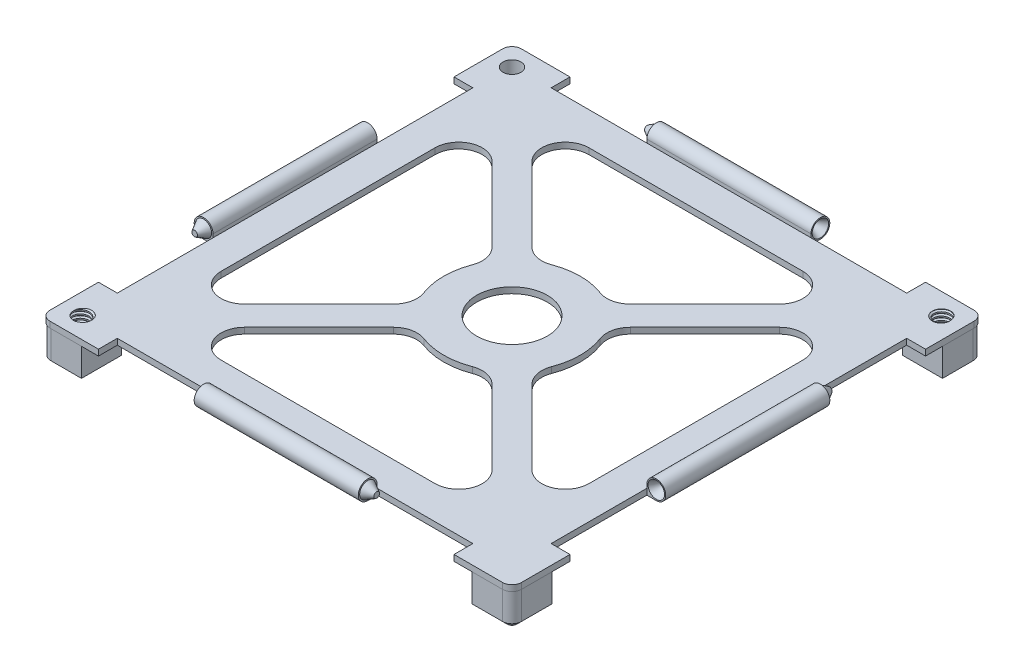
SolidWorks part; units mm, degrees
material "6061 Alloy"
ref_plane "Front Plane" through (0, 0, 0) normal (0, 0, 1) x (1, 0, 0)
ref_plane "Top Plane" through (0, 0, 0) normal (0, 1, 0) x (1, 0, 0)
ref_plane "Right Plane" through (0, 0, 0) normal (1, 0, 0) x (0, 0, -1)
sketch "X-Axis" plane through (0, 0, 0) normal (0, 1, 0) x (1, 0, 0)
  line L2 (-10, 0) -> (10, 0)
  point P3 (0, 0)
  dimension "D1" = 20
sketch "Y-Axis" plane through (0, 0, 0) normal (0, 1, 0) x (1, 0, 0)
  line L0 (0, -10) -> (0, 10)
  dimension "D1" = 20
sketch "Z-Axis" plane through (0, 0, 0) normal (1, 0, 0) x (0, 0, -1)
  line L0 (0, 10) -> (0, -10)
  line L1 (0, 55) -> (0, -55) construction
  point P5 (0, 0)
  dimension "D1" = 20
ref_axis "Axis1" through (0, 0, 0) along (0, 1, 0)
sketch "Sketch1" plane through (0, 0, 0) normal (0, 1, 0) x (1, 0, 0)
  line L0 (-10.4535, 14.6961) -> (-26.2218, 30.4645)
  line L1 (-46, -46) -> (46, -46)
  line L2 (-46, -46) -> (-46, 46)
  line L3 (-46, 46) -> (46, 46)
  line L4 (46, -46) -> (46, 46)
  line L5 (-46, -46) -> (46, 46) construction
  line L6 (-46, 46) -> (46, -46) construction
  line L7 (-22.6863, 39) -> (22.6863, 39)
  line L8 (26.2218, 30.4645) -> (10.4535, 14.6961)
  line L9 (30.4645, -26.2218) -> (14.6961, -10.4535)
  line L10 (14.6961, 10.4535) -> (30.4645, 26.2218)
  line L11 (39, 22.6863) -> (39, -22.6863)
  line L12 (-26.2218, -30.4645) -> (-10.4535, -14.6961)
  line L13 (10.4535, -14.6961) -> (26.2218, -30.4645)
  line L14 (22.6863, -39) -> (-22.6863, -39)
  line L15 (-30.4645, 26.2218) -> (-14.6961, 10.4535)
  line L16 (-14.6961, -10.4535) -> (-30.4645, -26.2218)
  line L17 (-39, -22.6863) -> (-39, 22.6863)
  circle A0 centre (0, 0) radius 7.5
  arc A1 (-5.1441, 13.5569) -> (5.1441, 13.5569) centre (0, 0) cw
  arc A2 (-5.1441, 13.5569) -> (-10.4535, 14.6961) centre (-6.9179, 18.2316) cw
  arc A3 (5.1441, 13.5569) -> (10.4535, 14.6961) centre (6.9179, 18.2316) ccw
  arc A4 (22.6863, 39) -> (26.2218, 30.4645) centre (22.6863, 34) cw
  arc A5 (-26.2218, 30.4645) -> (-22.6863, 39) centre (-22.6863, 34) cw
  arc A6 (13.5569, -5.1441) -> (14.6961, -10.4535) centre (18.2316, -6.9179) ccw
  arc A7 (13.5569, 5.1441) -> (13.5569, -5.1441) centre (0, 0) cw
  arc A8 (13.5569, 5.1441) -> (14.6961, 10.4535) centre (18.2316, 6.9179) cw
  arc A9 (30.4645, 26.2218) -> (39, 22.6863) centre (34, 22.6863) cw
  arc A10 (39, -22.6863) -> (30.4645, -26.2218) centre (34, -22.6863) cw
  arc A11 (-5.1441, -13.5569) -> (-10.4535, -14.6961) centre (-6.9179, -18.2316) ccw
  arc A12 (5.1441, -13.5569) -> (-5.1441, -13.5569) centre (0, 0) cw
  arc A13 (5.1441, -13.5569) -> (10.4535, -14.6961) centre (6.9179, -18.2316) cw
  arc A14 (26.2218, -30.4645) -> (22.6863, -39) centre (22.6863, -34) cw
  arc A15 (-22.6863, -39) -> (-26.2218, -30.4645) centre (-22.6863, -34) cw
  arc A16 (-13.5569, 5.1441) -> (-14.6961, 10.4535) centre (-18.2316, 6.9179) ccw
  arc A17 (-13.5569, -5.1441) -> (-13.5569, 5.1441) centre (0, 0) cw
  arc A18 (-13.5569, -5.1441) -> (-14.6961, -10.4535) centre (-18.2316, -6.9179) cw
  arc A19 (-30.4645, -26.2218) -> (-39, -22.6863) centre (-34, -22.6863) cw
  arc A20 (-39, 22.6863) -> (-30.4645, 26.2218) centre (-34, 22.6863) cw
  point P0 (0, 0)
  point P59 (0, 0)
  dimension "D3" = 15
  dimension "D6" = 7
  dimension "D8" = 5
  dimension "D1" = 92
  dimension "D2" = 92
  dimension "D4" = 6
  dimension "D5" = 6
  dimension "D7" = 7
  dimension "D9" = 4
extrude "Boss-Extrude1" add sketch "Sketch1" along normal blind 1.27
sketch "Sketch6" plane through (0, 0, 0) normal (0, 0, 1) x (1, 0, 0)
  line L0 (46, 2) -> (46, 0)
  line L1 (46, 0) -> (48, 0)
  line L2 (0, 0) -> (0, 69.0457) construction
  arc A0 (46, 2) -> (48, 0) centre (48, 2) cw
  dimension "D1" = 50
extrude "Boss-Extrude3" add sketch "Sketch6" along normal mid plane 34.8
sketch "Sketch7" plane through (0, 0, 17.4) normal (0, 0, 1) x (1, 0, 0)
  circle A0 centre (48, 2) radius 1.75
  dimension "D1" = 3.5
extrude "Cut-Extrude2" cut sketch "Sketch7" against normal blind 2 draft 30
sketch "Sketch8" plane through (0, 0, -17.4) normal (0, 0, -1) x (-1, 0, 0)
  circle A0 centre (-48, 2) radius 1.7
  dimension "D1" = 3.4
extrude "Boss-Extrude4" add sketch "Sketch8" along normal blind 1.9 draft 30
pattern_circular "CirPattern1" count 4 over 360 about axis through (0, 0, 0) along (0, 1, 0) of "Boss-Extrude3", "Cut-Extrude2", "Boss-Extrude4"
sketch "Sketch16" plane through (0, 0, 0) normal (0, -1, 0) x (1, 0, 0)
  line L1 (-50, 50) -> (-37.7, 50)
  line L2 (-50, 50) -> (-50, 37.7)
  line L3 (-50, 37.7) -> (-37.7, 37.7)
  line L4 (-37.7, 50) -> (-37.7, 37.7)
  dimension "D1" = 50
  dimension "D2" = 50
  dimension "D3" = 37.7
extrude "Boss-Extrude6" add sketch "Sketch16" against normal up to surface (1.27 mm away) up to face at (0, 1.27, 24.6467)
pattern_circular "CirPattern3" count 4 over 360 about axis through (0, 0, 0) along (0, 1, 0) of "Boss-Extrude6"
fillet "Fillet1" radius 2 4 edges at (-50, 0.635, -50) (50, 0.635, -50) (50, 0.635, 50) (-50, 0.635, 50)
sketch "Sketch10" plane through (0, 0, 0) normal (0, -1, 0) x (1, 0, 0)
  line L1 (-47.9, 49.9) -> (-41.4, 49.9)
  line L2 (-49.9, 47.9) -> (-49.9, 41.4)
  line L3 (-49.9, 41.4) -> (-41.4, 41.4)
  line L4 (-41.4, 49.9) -> (-41.4, 41.4)
  line L6 (-37.7, 50) -> (-48, 50) construction
  line L7 (-50, 48) -> (-50, 37.7) construction
  arc A0 (-47.9, 49.9) -> (-49.9, 47.9) centre (-47.9, 47.9) ccw
  dimension "D4" = 2
  dimension "D1" = 0.1
  dimension "D2" = 0.1
  dimension "D3" = 8.5
extrude "Boss-Extrude5" add sketch "Sketch10" along normal blind 7
chamfer "Chamfer1" distance 1 angle 45 5 edges at (-45.65, -7, 41.4) (-49.9, -7, 44.65) (-49.3142, -7, 49.3142) (-44.65, -7, 49.9) (-41.4, -7, 45.65)
pattern_circular "CirPattern2" count 4 over 360 about axis through (0, 0, 0) along (0, 1, 0) of "Boss-Extrude5", "Chamfer1"
sketch "Sketch11" plane through (0, -7, 0) normal (0, -1, 0) x (1, 0, 0)
  line L0 (-48.9, 42.4) -> (-42.4, 48.9)
  point P4 (-45.65, 45.65)
hole_wizard "Tap Drill for #8-32 Tap1" positions "3DSketch1" profile "Sketch12" hole size "#8-32" standard "ANSI Inch"
sketch3d "3DSketch1"
  point P0 (-45.65, -7, 45.65)
sketch "Sketch12" plane through (-45.65, -7, 45.65) normal (1, 0, 0) x (0, 0, -1)
  line L0 (0, 0) -> (0, 11.0378)
  line L1 (0, 11.0378) -> (1.7272, 10)
  line L2 (1.7272, 10) -> (1.7272, 0)
  line L5 (1.7272, 0) -> (0, 0)
  line L10 (0, 11.0378) -> (-1.7272, 10) construction
  line L11 (0, -6.35) -> (0, 107.95) construction
  dimension "Hole Dia." = 3.4544
  dimension "Hole Depth" = 10
  dimension "Drill Angle" = 118
ref_axis "Axis2" through (-45.65, 1.27, 45.65) along (0, -1, 0)
ref_plane "Plane1" through (0, -9, 0) normal (0, -1, 0) x (-1, 0, 0)
sketch "Sketch13" plane through (0, -9, 0) normal (0, -1, 0) x (1, 0, 0)
  circle A0 centre (-45.65, 45.65) radius 1.7272 construction
  circle A1 centre (-45.65, 45.65) radius 1.7272
curve "Helix/Spiral1" pitch 0.7937 height 11.9062 radius 1.7272 centre (-45.65, -9, 45.65) axis (0, 1, 0) start towards (0, 0, -1)
ref_plane "Plane2" through (-45.65, -9, 43.9228) normal (-0.9973, 0.0729, 0) x (0, 0, 1)
sketch "Sketch14" plane through (-45.65, -9, 43.9228) normal (-0.9973, 0.0729, 0) x (0, 0, 1)
  line L0 (-0.3556, 0.0496) -> (-0.3556, -0.0496)
  line L1 (-0.3556, -0.0496) -> (0.074, -0.2977)
  line L2 (0.074, -0.2977) -> (0.074, 0.2977)
  line L3 (0.074, 0.2977) -> (-0.3556, 0.0496)
  line L4 (0, 0) -> (1.0276, 0) construction
  line L5 (1.7272, 10.2426) -> (1.7272, 1.9947) construction
  point P0 (0, 0)
  point P8 (0.074, 0)
  dimension "D1" = 60
  dimension "D2" = 30
  dimension "D3" = 0.0992
  dimension "D4" = 2.0828
  dimension "D5" = 0.4296
sweep "Cut-Sweep3" cut profiles "Sketch14" path "Helix/Spiral1"
sketch "Sketch15" plane through (0, -7, 0) normal (0, -1, 0) x (1, 0, 0)
  line L0 (-48.9, -42.4) -> (-42.4, -48.9) construction
  circle A0 centre (-45.65, -45.65) radius 1.905
  point P9 (-45.65, -45.65)
  dimension "D1" = 3.81
extrude "Cut-Extrude3" cut sketch "Sketch15" against normal through all
pattern_circular "CirPattern4" count 2 over 360 about axis through (0, 1.27, 0) along (0, -1, 0) of "Tap Drill for #8-32 Tap1", "Cut-Sweep3"
